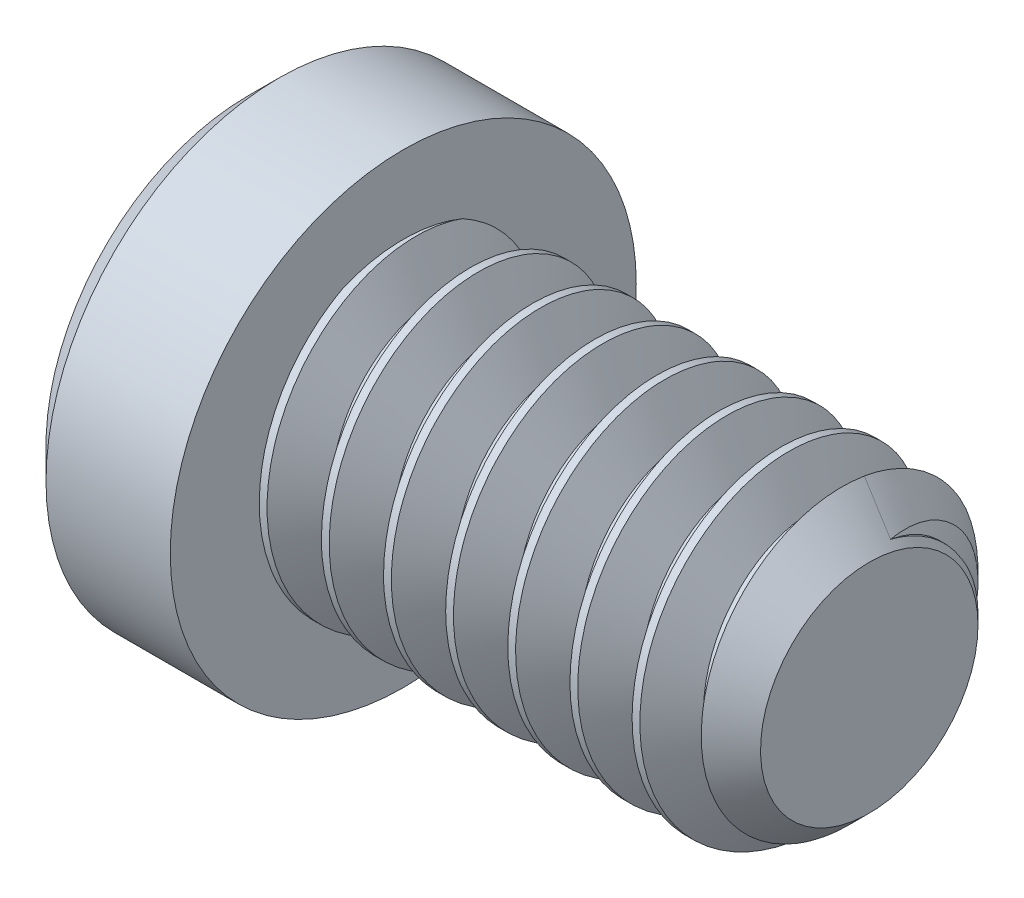
SolidWorks part; units mm, degrees
ref_plane "Front Plane" through (0, 0, 0) normal (0, 0, 1) x (1, 0, 0)
ref_plane "Top Plane" through (0, 0, 0) normal (0, 1, 0) x (1, 0, 0)
ref_plane "Right Plane" through (0, 0, 0) normal (1, 0, 0) x (0, 0, -1)
sketch "Sketch1" plane through (0, 0, 0) normal (0, 0, 1) x (1, 0, 0)
  line L0 (4.7625, 0) -> (-4.7625, 0) construction
  line L1 (4.7625, 3.175) -> (4.7625, -3.175) construction
  line L2 (-4.7625, 4.7625) -> (-4.7625, -4.7625) construction
  line L3 (-4.7625, 4.7625) -> (-7.3025, 4.7625) construction
  line L4 (-7.3025, 4.7625) -> (-7.9375, 4.1275) construction
  line L5 (-7.9375, 4.1275) -> (-7.9375, -4.1275) construction
  line L6 (-7.9375, -4.1275) -> (-7.3025, -4.7625) construction
  line L7 (-7.3025, -4.7625) -> (-4.7625, -4.7625) construction
  point P7 (-5.5499, 0)
  point P12 (-0.3175, -3.175)
  dimension "D1" = 45
  dimension "Dec." = 6.35
  dimension "Length" = 9.525
  dimension "Head Dia" = 9.525
  dimension "Head Height" = 3.175
  dimension "Hex Depth" = 2.3876
  dimension "Chamfer" = 0.635
  dimension "D2" = 5.08
ref_plane "Plane1" through (4.7625, 0, 0) normal (1, 0, 0) x (0, 0, -1)
ref_plane "Plane2" through (-7.9375, 0, 0) normal (1, 0, 0) x (0, 0, -1)
sketch "Sketch2" plane through (4.7625, 0, 0) normal (1, 0, 0) x (0, 0, -1)
  circle A0 centre (0, 0) radius 3.175
extrude "Boss-Extrude1" add sketch "Sketch2" against normal up to vertex (9.525 mm away) up to point (-4.7625, 0, 0)
sketch "Sketch3" plane through (4.7625, 0, 0) normal (1, 0, 0) x (0, 0, -1)
  circle A0 centre (0, 0) radius 3.175 construction
  circle A1 centre (0, 0) radius 3.175
curve "Helix/Spiral1" pitch 1.27 height 10.795 radius 3.175 centre (4.7625, 0, 0) axis (-1, 0, 0) start towards (0, 1, 0) parameters "Pitch"=1.27
chamfer "Chamfer1" distance 0.9525 angle 45 1 edges at (4.7625, 0, -3.175)
sketch "Sketch5" plane through (0, 0, 0) normal (0, 0, 1) x (1, 0, 0)
  line L0 (4.2069, 3.175) -> (5.3181, 3.175)
  line L1 (5.3181, 3.175) -> (4.8419, 2.3501)
  line L2 (4.8419, 2.3501) -> (4.6831, 2.3501)
  line L3 (4.6831, 2.3501) -> (4.2069, 3.175)
  line L4 (4.7625, 2.3501) -> (4.7625, 3.175) construction
  line L5 (4.445, 2.7626) -> (5.08, 2.7626) construction
  dimension "D1" = 60
  dimension "D2" = 0.635
  dimension "D3" = 0.1588
sweep "Cut-Sweep1" cut profiles "Sketch5" path "Helix/Spiral1" align with end faces yes
sketch "Sketch4" plane through (-7.9375, 0, 0) normal (1, 0, 0) x (0, 0, -1)
  line L0 (-4.7625, 0.7937) -> (4.7625, 0.7937) construction
  line L1 (0, 1.8331) -> (-1.5875, 0.9165)
  line L2 (-1.5875, 0.9165) -> (-1.5875, -0.9165)
  line L3 (-1.5875, -0.9165) -> (0, -1.8331)
  line L4 (0, -1.8331) -> (1.5875, -0.9165)
  line L5 (1.5875, -0.9165) -> (1.5875, 0.9165)
  line L6 (1.5875, 0.9165) -> (0, 1.8331)
  line L7 (0, 0) -> (0, 0.7937) construction
  circle A0 centre (0, 0) radius 1.5875 construction
  dimension "Hex Size" = 3.175
  dimension "D1" = 9.525
  dimension "D2" = 0.7937
sketch "Sketch6" plane through (0, 0, 0) normal (0, 0, 1) x (1, 0, 0)
  line L0 (-7.3025, 4.7625) -> (-7.9375, 4.1275) construction
  line L1 (-4.7625, 4.7625) -> (-7.3025, 4.7625) construction
  line L2 (-4.7625, 4.7625) -> (-4.7625, -4.7625) construction
  line L3 (-7.9375, 4.1275) -> (-7.9375, -4.1275) construction
  line L4 (-7.3025, 4.7625) -> (-7.9375, 4.1275)
  line L5 (-4.7625, 4.7625) -> (-7.3025, 4.7625)
  line L6 (-4.7625, 4.7625) -> (-4.7625, 0)
  line L7 (-7.9375, 4.1275) -> (-7.9375, 0)
  line L8 (-4.7625, 0) -> (-7.9375, 0) construction
  line L9 (-4.7625, 0) -> (-7.9375, 0)
revolve "Revolve1" add sketch "Sketch6" angle 360 about L8
extrude "Cut-Extrude1" cut sketch "Sketch4" along normal up to vertex (2.3876 mm away) up to point (-5.5499, 0, 0)
sketch "Sketch8" plane through (-7.9375, 0, 0) normal (-1, 0, 0) x (0, 0, 1)
  circle A1 centre (0, 0) radius 1.8331
extrude "Cut-Extrude2" cut sketch "Sketch8" against normal through all draft 45
move or copy body "Body-Move/Copy1" [suppressed] bodies to move or copy 105
equation "\"D3@Helix/Spiral1\" = \"Length@Sketch1\"+\"Pitch@Helix/Spiral1\""
equation "\"D3@Sketch5\" = \"Pitch@Helix/Spiral1\"*.125"
equation "\"D2@Sketch5\" = \"Pitch@Helix/Spiral1\"*.50"
equation "\"D1@Chamfer1\" = \"Pitch@Helix/Spiral1\"*.75"
equation "\"D2@Sketch1\" = \"Pitch@Helix/Spiral1\"*4"
equation "\"D1@Sketch4\" = \"Head Dia@Sketch1\""
